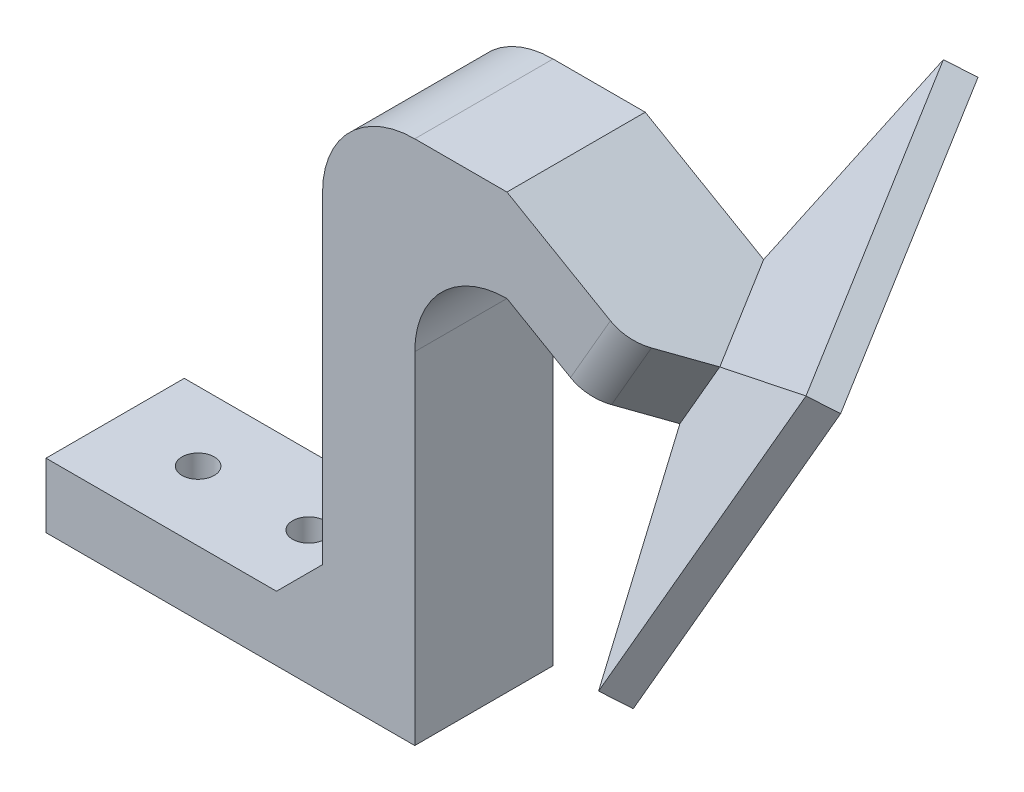
SolidWorks part; units mm, degrees
ref_plane "前视基准面" through (0, 0, 0) normal (0, 0, 1) x (1, 0, 0)
ref_plane "上视基准面" through (0, 0, 0) normal (0, 1, 0) x (1, 0, 0)
ref_plane "右视基准面" through (0, 0, 0) normal (1, 0, 0) x (0, 0, -1)
other "Configuration Table"
sketch "草图1" plane through (0, 0, 0) normal (0, 1, 0) x (1, 0, 0)
  line L0 (-35, 7.5) -> (-35, -7.5)
  line L1 (5, 7.5) -> (-35, 7.5)
  line L2 (5, -7.5) -> (-35, -7.5)
  line L3 (5, 7.5) -> (5, -7.5)
  point P4 (0, 0)
  point P8 (-15, -7.5)
  point P12 (-15, 7.5)
extrude "凸台-拉伸1" add sketch "草图1" along normal blind 7
sketch3d "3D草图1"
  point P0 (-7.8084, 7, -3.4058)
ref_plane "基准面1" through (0, 7, 0) normal (0, 1, 0) x (1, 0, 0)
sketch "草图3" plane through (0, 7, 0) normal (0, 1, 0) x (1, 0, 0)
  line L4 (-5, -3) -> (-5, 3)
  line L9 (-5, 3) -> (5, 3)
  line L10 (-5, -3) -> (5, -3)
  line L11 (5, 3) -> (5, -3)
  point P3 (-5, 0)
  point P4 (0, 0)
  point P6 (0, 0)
  point P13 (-5, 0)
extrude "凸台-拉伸2" add sketch "草图3" along normal blind 50
sketch3d "3D草图2"
  point P0 (1.3021, 37.2317, 3)
ref_plane "基准面2" through (0, 0, 3) normal (0, 0, 1) x (1, 0, 0)
sketch "草图4" plane through (0, 0, 3) normal (0, 0, 1) x (1, 0, 0)
  line L4 (5, 57) -> (5, 7) construction
  line L7 (5, 57) -> (5, 47)
  line L8 (5, 47) -> (15, 47)
  line L9 (5, 57) -> (15, 57)
  line L11 (15, 47) -> (19.3301, 54.5)
  line L12 (15, 57) -> (19.3301, 54.5)
extrude "凸台-拉伸5" add sketch "草图4" against normal blind 6
fillet "圆角1" radius 10 1 edges at (-5, 57, 0) type face fillet first side face at (5, 57, 0) second side face at (-5, 32, 0)
sketch3d "3D草图3"
  point P0 (5, 20.7331, -0.0874)
ref_plane "基准面3" through (5, 0, 0) normal (1, 0, 0) x (0, 0, -1)
sketch "草图7" plane through (0, 7, 0) normal (0, 1, 0) x (1, 0, 0)
  circle A0 centre (-26, 0) radius 1.75
  circle A1 centre (-14, 0) radius 1.75
extrude "切除-拉伸3" cut sketch "草图7" against normal blind 10
sketch3d "3D草图4"
  point P0 (-5.777, 3.751, -7.5)
sketch3d "3D草图5"
  point P0 (1.0785, 19.5385, -3)
ref_plane "基准面5" through (0, 0, -3) normal (0, 0, -1) x (-1, 0, 0)
sketch3d "3D草图6"
  point P0 (15.8579, 48.4859, 0.3319)
ref_plane "基准面6" through (-17.0305, 29.4977, 0) normal (0.5, -0.866, 0) x (0.866, 0.5, 0)
sketch3d "3D草图7"
  point P0 (19.8357, 54.2081, 0.8937)
sketch "草图16" plane through (-9.1016, 5.2548, 0) normal (0.866, -0.5, 0) x (0, 0, -1)
  line L0 (-3, 56.8634) -> (3, 56.8634)
  line L1 (3, 56.8634) -> (3, 48.2032)
  line L2 (3, 48.2032) -> (-3, 48.2032)
  line L3 (-3, 48.2032) -> (-3, 56.8634)
extrude "凸台-拉伸11" add sketch "草图16" along normal blind 10
sketch "草图17" plane through (28.4317, 49.2452, 0) normal (0.5, 0.866, 0) x (0.866, -0.5, 0)
  line L0 (-0.5096, -3) -> (6.5614, 4.0711)
  line L2 (-0.5096, 3) -> (-0.5096, -3)
  line L4 (6.5614, 4.0711) -> (4.3874, 7.7861)
  line L5 (-0.5096, 3) -> (4.3874, 7.7861)
extrude "凸台-拉伸12" add sketch "草图17" against normal blind 8.66
sketch "草图19" plane through (5.7697, -3.3311, -3.8988) normal (0.7474, -0.4315, -0.5051) x (-0.6557, -0.3569, -0.6654)
  line L0 (-36.0623, 43.9659) -> (-32.7438, 46.7074) construction
  line L1 (-38.0139, 42.3536) -> (-32.4984, 35.6772) construction
  line L2 (-33.9281, 69.2973) -> (-5.2677, 34.6046)
  line L3 (-33.9281, 69.2973) -> (-60.9113, 47.0059)
  line L4 (-60.9113, 47.0059) -> (-32.2509, 12.3132)
  line L7 (-5.2677, 34.6046) -> (-32.2509, 12.3132)
  point P0 (-34.4031, 45.3367)
  point P1 (-35.2561, 39.0154)
  point P4 (-33.0895, 40.8052)
  point P11 (-33.0895, 40.8052)
  point P13 (-47.4197, 58.1516)
extrude "凸台-拉伸14" add sketch "草图19" along normal blind 3
ref_plane "基准面7" through (0, 0, 20) normal (0, 0, 1) x (1, 0, 0)
sketch "草图20" plane through (0, 0, -3) normal (0, 0, -1) x (-1, 0, 0)
  line L0 (-5, 7) -> (5, 7)
  line L1 (5, 7) -> (5, 47)
  line L2 (-5, 47) -> (-5, 7)
  line L3 (-15, 47) -> (-5, 47)
  line L7 (-5, 57) -> (-15, 57)
  line L11 (-27.9904, 49.5) -> (-15, 57)
  line L12 (-15, 47) -> (-23.6604, 42.0002)
  line L13 (-23.6604, 42.0002) -> (-27.9904, 49.5)
  arc A0 (5, 47) -> (-5, 57) centre (-5, 47) ccw
extrude "凸台-拉伸15" add sketch "草图20" along normal blind 4.5 and the other way blind 10.5
sketch "草图21" plane through (28.4317, 49.2452, 0) normal (0.5, 0.866, 0) x (0.866, -0.5, 0)
  line L0 (-0.5096, 7.5) -> (-0.5096, 3)
  line L1 (-0.5096, 3) -> (-0.5096, 7.5) construction
  line L2 (-0.5096, 3) -> (4.3874, 7.7861)
  line L3 (4.3874, 7.7861) -> (-0.5096, 7.5)
  line L4 (-0.5096, -7.5) -> (8.2964, 1.1064)
  line L5 (-2.4182, 19.4155) -> (15.2594, -10.7921) construction
  line L6 (6.5614, 4.0711) -> (8.2964, 1.1064)
  line L7 (-0.5096, -3) -> (-0.5096, -7.5)
  line L8 (-0.5096, -3) -> (6.5614, 4.0711)
extrude "凸台-拉伸17" add sketch "草图21" against normal blind 8.66
sketch "草图22" plane through (28.4317, 49.2452, 0) normal (0.5, 0.866, 0) x (0.866, -0.5, 0)
  line L25 (4.3874, 7.7861) -> (-2.4182, 19.4155)
  line L29 (8.2964, 1.1064) -> (15.2594, -10.7921)
  line L33 (-2.4182, 19.4155) -> (-0.5096, 7.5)
  line L34 (-0.5096, 7.5) -> (4.3874, 7.7861)
  line L35 (15.2594, -10.7921) -> (4.9677, -2.1468)
  line L36 (-0.5096, -7.5) -> (8.2964, 1.1064) construction
  line L37 (4.9677, -2.1468) -> (8.2964, 1.1064)
extrude "凸台-拉伸22" add sketch "草图22" against normal blind 8.66
sketch "草图23" plane through (0, 0, 7.5) normal (0, 0, 1) x (1, 0, 0)
  line L0 (-5, 7) -> (-10, 7)
  line L1 (-35, 7) -> (-5, 7) construction
  line L2 (-5, 7) -> (-5, 12)
  line L3 (-5, 7) -> (-5, 47) construction
  line L4 (-5, 12) -> (-10, 7)
extrude "凸台-拉伸23" add sketch "草图23" against normal blind 15
fillet "圆角2" radius 10 1 edges at (5, 47, 0) type face fillet first side face at (11.6667, 47, 0) second side face at (5, 23.5, 0)
sketch "草图24" plane through (7.4453, -4.2986, 14.6909) normal (0.4374, -0.2525, 0.8631) x (0.8993, 0.1228, -0.4198)
  line L0 (34.2791, 45.4825) -> (38.0327, 42.9715)
  line L1 (38.0327, 42.9715) -> (48.1354, 58.0739)
  line L2 (48.1354, 58.0739) -> (34.2791, 45.4825)
  line L3 (29.464, 38.2845) -> (33.2176, 35.7736)
  line L4 (33.2176, 35.7736) -> (23.1149, 20.671)
  line L5 (23.1149, 20.671) -> (29.464, 38.2845)
extrude "凸台-拉伸24" add sketch "草图24" against normal blind 35
sketch "草图25" plane through (28.4317, 49.2452, 0) normal (-0.5, -0.866, 0) x (0.866, -0.5, 0)
  line L0 (11.3617, 13.073) -> (15.2594, 10.7921)
  line L1 (15.2594, 10.7921) -> (4.9677, 2.1468)
  line L2 (4.9677, 2.1468) -> (11.3617, 13.073)
extrude "切除-拉伸4" cut sketch "草图25" against normal blind 35 and the other way blind 35
sketch "草图26" plane through (24.1017, 41.7454, 0) normal (0.5, 0.866, 0) x (0.866, -0.5, 0)
  line L0 (-0.6776, 7.5) -> (-2.4182, 19.4155)
  line L1 (-2.4182, 19.4155) -> (-6.3158, 17.1346)
  line L2 (-6.3158, 17.1346) -> (-0.6776, 7.5)
extrude "切除-拉伸5" cut sketch "草图26" against normal blind 35 and the other way blind 35
fillet "圆角3" radius 5 1 edges at (25.8254, 45.7501, 7.5) type face fillet first side face at (0.2091, 30.5535, 7.5) second side face at (28.1971, 44.3808, 4.8234)
